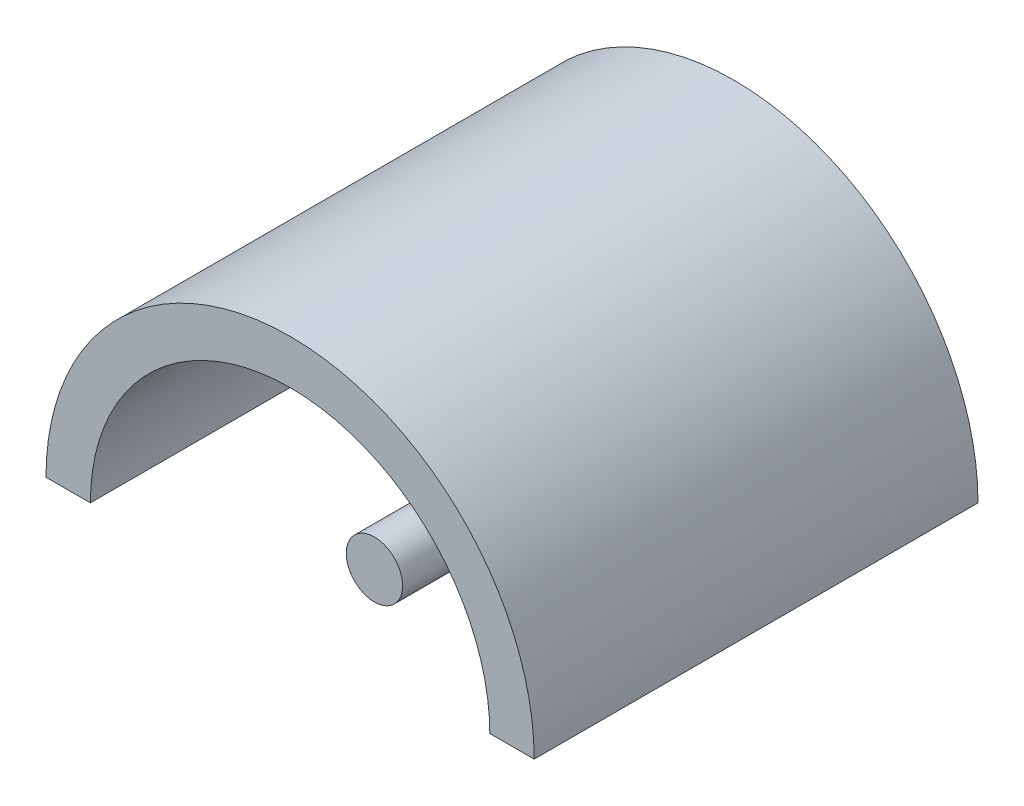
SolidWorks part; units mm, degrees
ref_plane "Ebene vorne" through (0, 0, 0) normal (0, 0, 1) x (1, 0, 0)
ref_plane "Ebene oben" through (0, 0, 0) normal (0, 1, 0) x (1, 0, 0)
ref_plane "Ebene rechts" through (0, 0, 0) normal (1, 0, 0) x (0, 0, -1)
sketch "Skizze1" plane through (0, 0, 0) normal (0, 0, 1) x (1, 0, 0)
  line L1 (-110, 0) -> (-90, 0)
  line L2 (110, 0) -> (90, 0)
  arc A0 (-110, 0) -> (110, 0) centre (0, 0) cw
  arc A1 (-90, 0) -> (90, 0) centre (0, 0) cw
  point P4 (0, 0)
  dimension "D1" = 220
  dimension "D2" = 20
extrude "Aufsatz-Linear austragen1" add sketch "Skizze1" along normal blind 200
sketch "Skizze2" plane through (0, 0, 0) normal (0, 1, 0) x (1, 0, 0)
  line L1 (5, -30) -> (-5, -30)
  line L2 (5, -30) -> (5, -45)
  line L3 (5, -45) -> (-5, -45)
  line L4 (-5, -30) -> (-5, -45)
  point P4 (0, -30)
  dimension "D1" = 15
  dimension "D2" = 10
  dimension "D3" = 30
extrude "Aufsatz-Linear austragen2" add sketch "Skizze2" along normal up to next
sketch "Skizze4" plane through (-5, 0, 0) normal (-1, 0, 0) x (0, 0, 1)
  line L0 (45, 89.861) -> (45, 0) construction
  line L1 (30, 0) -> (45, 0)
  line L2 (30, 0) -> (30, 10)
  line L3 (30, 10) -> (45, 10)
  line L4 (45, 0) -> (45, 10)
  dimension "D1" = 10
extrude "Aufsatz-Linear austragen3" add sketch "Skizze4" along normal up to next
mirror "Spiegeln1" about plane through (0, 0, 0) normal (1, 0, 0) of "Aufsatz-Linear austragen3"
sketch "Skizze5" plane through (0, 0, 30) normal (0, 0, -1) x (-1, 0, 0)
  line L0 (-90, 0) -> (90, 0) construction
  circle A0 centre (0, 0) radius 22
  dimension "D1" = 44
extrude "Aufsatz-Linear austragen4" add sketch "Skizze5" against normal blind 40
sketch "Skizze6" plane through (0, 0, 70) normal (0, 0, 1) x (1, 0, 0)
  circle A0 centre (0, 0) radius 12.7
extrude "Aufsatz-Linear austragen5" add sketch "Skizze6" along normal blind 92
fillet "Verrundung2" radius 5 12 edges at (5, 55.6426, 30) (-5, 55.6426, 30) (-5, 55.6426, 45) (5, 55.6426, 45) (56, 0, 30) (54.5193, 10, 45) (56, 0, 45) (54.5193, 10, 30) (-54.5193, 10, 30) (-56, 0, 30) (-56, 0, 45) (-54.5193, 10, 45) second distance 5 conic rho 0.3 first distance on face at (0, 20.3291, 30) first distance on face at (0, 55.8213, 45) first distance on face at (55.4426, 5.0376, 45) first distance on face at (-55.4426, 5.0376, 45)
